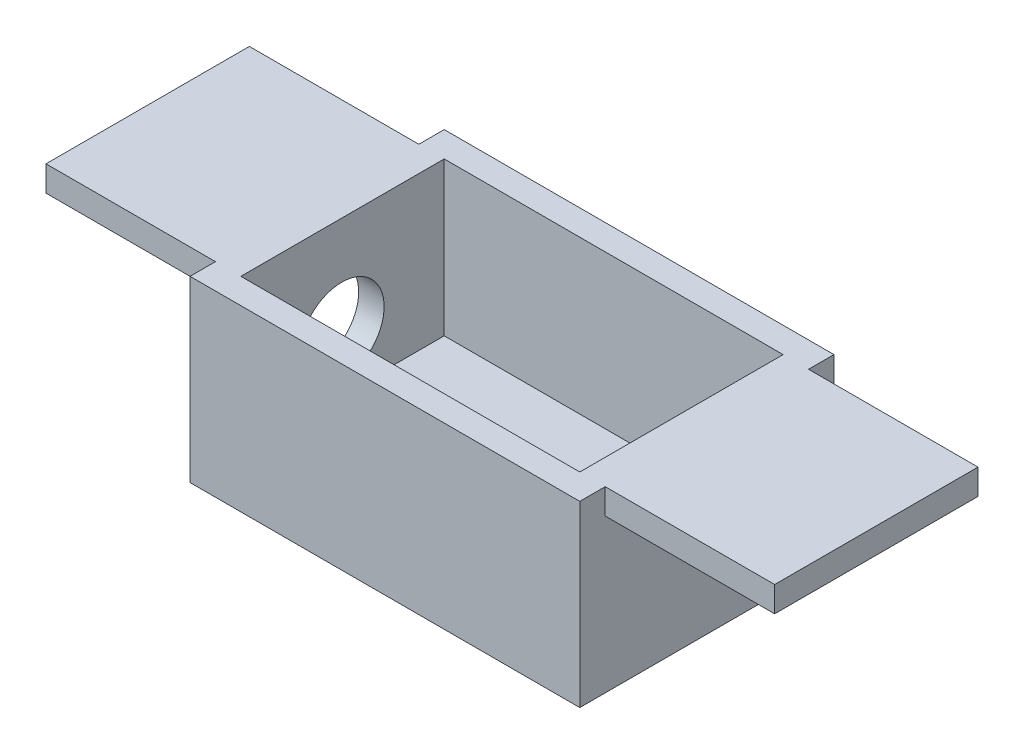
SolidWorks part; units mm, degrees
ref_plane "前视基准面" through (0, 0, 0) normal (0, 0, 1) x (1, 0, 0)
ref_plane "上视基准面" through (0, 0, 0) normal (0, 1, 0) x (1, 0, 0)
ref_plane "右视基准面" through (0, 0, 0) normal (1, 0, 0) x (0, 0, -1)
sketch "草图1" plane through (0, 0, 0) normal (0, 0, 1) x (1, 0, 0)
  line L0 (-66, 28.8935) -> (-43, 28.8935)
  line L1 (-43, 28.8935) -> (-43, 10.812)
  line L2 (-43, 10.812) -> (-3, 10.812)
  line L3 (-3, 10.812) -> (-3, 28.8935)
  line L4 (-3, 28.8935) -> (20, 28.8935)
  line L5 (-66, 28.8935) -> (-66, 25.8935)
  line L6 (-66, 25.8935) -> (-46, 25.8935)
  line L7 (-46, 25.8935) -> (-46, 7.812)
  line L8 (-46, 7.812) -> (0, 7.812)
  line L9 (0, 7.812) -> (0, 25.8935)
  line L10 (0, 25.8935) -> (20, 25.8935)
  line L11 (20, 25.8935) -> (20, 28.8935)
  dimension "D1" = 3
  dimension "D2" = 3
  dimension "D3" = 3
  dimension "D4" = 3
  dimension "D5" = 3
  dimension "D6" = 20
  dimension "D7" = 20
  dimension "D8" = 40
extrude "凸台-拉伸1" add sketch "草图1" along normal blind 24
sketch "草图2" plane through (0, 0, 24) normal (0, 0, 1) x (1, 0, 0)
  line L1 (20, 28.8935) -> (-3, 28.8935) construction
  line L2 (-46, 7.812) -> (0, 7.812)
  line L3 (-46, 7.812) -> (-46, 28.8935)
  line L4 (-46, 28.8935) -> (0, 28.8935)
  line L5 (0, 7.812) -> (0, 28.8935)
extrude "凸台-拉伸2" add sketch "草图2" along normal blind 3
sketch "草图3" plane through (0, 0, 0) normal (0, 0, -1) x (-1, 0, 0)
  line L0 (43, 28.8935) -> (66, 28.8935) construction
  line L1 (0, 7.812) -> (46, 7.812)
  line L2 (0, 7.812) -> (0, 28.8935)
  line L3 (0, 28.8935) -> (46, 28.8935)
  line L4 (46, 7.812) -> (46, 28.8935)
extrude "凸台-拉伸3" add sketch "草图3" along normal blind 3
sketch "草图6" plane through (-46, 0, 0) normal (-1, 0, 0) x (0, 0, 1)
  circle A0 centre (12.0936, 17.3392) radius 5
  dimension "D1" = 10
extrude "切除-拉伸2" cut sketch "草图6" against normal blind 10
